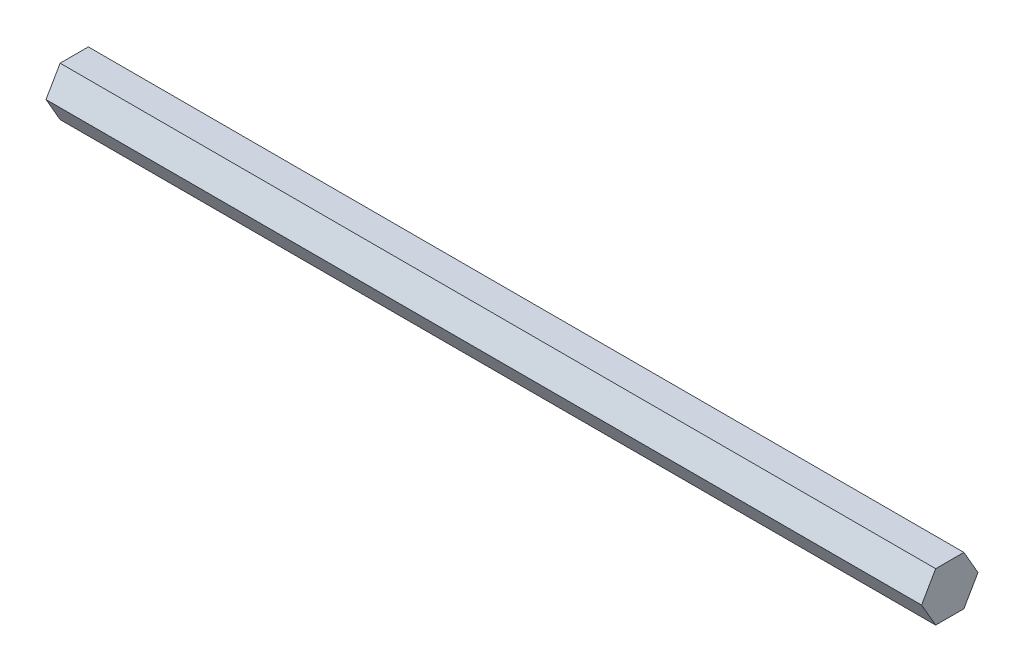
SolidWorks part; units mm, degrees
material "6061 Alloy"
ref_plane "Front" through (0, 0, 0) normal (0, 0, 1) x (1, 0, 0)
ref_plane "Top" through (0, 0, 0) normal (0, 1, 0) x (1, 0, 0)
ref_plane "Right" through (0, 0, 0) normal (1, 0, 0) x (0, 0, -1)
sketch "Sketch1" plane through (0, 0, 0) normal (1, 0, 0) x (0, 0, -1)
  line L1 (3.6662, 6.35) -> (-3.6662, 6.35)
  line L2 (-3.6662, 6.35) -> (-7.3323, 0)
  line L3 (-7.3323, 0) -> (-3.6662, -6.35)
  line L4 (-3.6662, -6.35) -> (3.6662, -6.35)
  line L5 (3.6662, -6.35) -> (7.3323, 0)
  line L6 (7.3323, 0) -> (3.6662, 6.35)
  circle A0 centre (0, 0) radius 6.35 construction
  dimension "D1" = 12.7
extrude "Boss-Extrude1" add sketch "Sketch1" along normal blind 227.5332
sketch "Sketch2" [suppressed] plane through (92.075, 0, 0) normal (1, 0, 0) x (0, 0, -1)
  circle A0 centre (0, 0) radius 2.413
  dimension "D1" = 4.826
extrude "Cut-Extrude1" [suppressed] cut sketch "Sketch2" against normal blind 25.4
sketch "Sketch3" [suppressed] plane through (0, 3.175, 5.4993) normal (0, 0.5, 0.866) x (1, 0, 0)
  line L0 (0, 3.6662) -> (0, -3.6662) construction
  line L1 (0, 0) -> (47.0154, 0) construction
  circle A0 centre (47.0154, 0) radius 1.778
  dimension "D2" = 3.556
  dimension "D1" = 47.0154
extrude "Cut-Extrude2" [suppressed] cut sketch "Sketch3" against normal blind 25.4
sketch "Sketch4" [suppressed] plane through (22.352, 0, 0) normal (1, 0, 0) x (0, 0, -1)
  circle A0 centre (0, 0) radius 2.54
  dimension "D1" = 5.08
extrude "Cut-Extrude3" [suppressed] cut sketch "Sketch4" against normal through all
